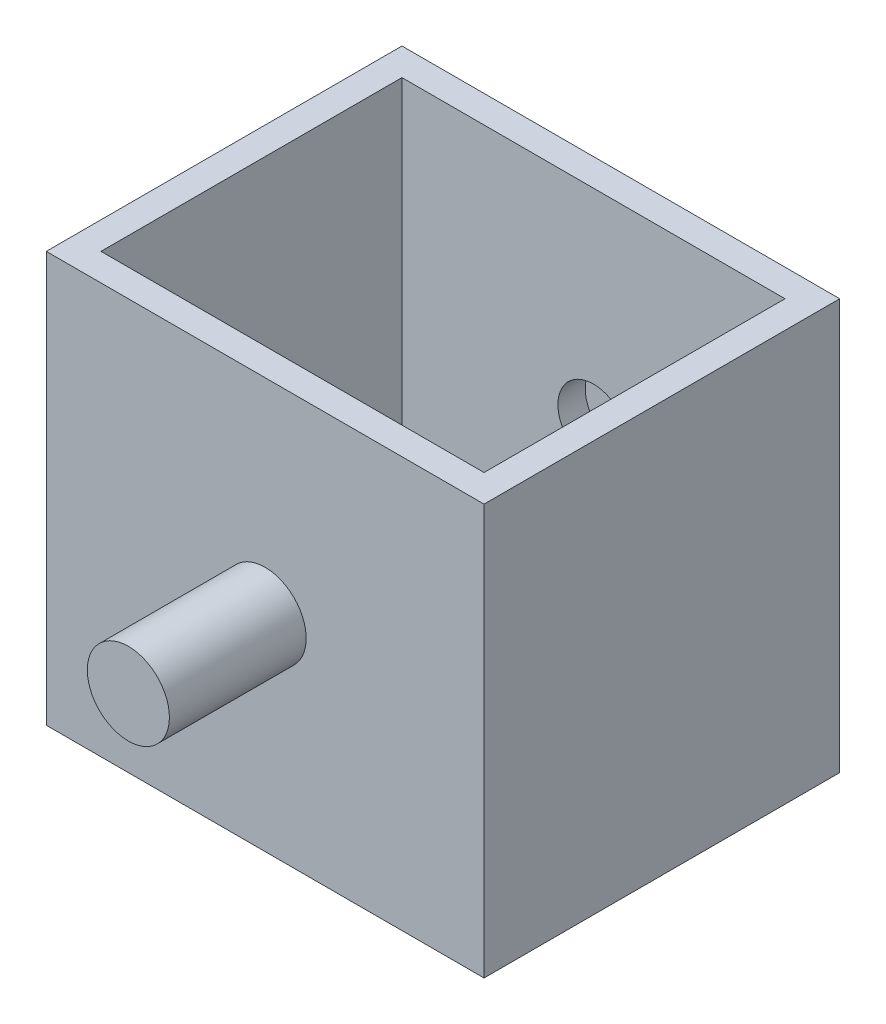
SolidWorks part; units mm, degrees
ref_plane "Front Plane" through (0, 0, 0) normal (0, 0, 1) x (1, 0, 0)
ref_plane "Top Plane" through (0, 0, 0) normal (0, 1, 0) x (1, 0, 0)
ref_plane "Right Plane" through (0, 0, 0) normal (1, 0, 0) x (0, 0, -1)
sketch "Sketch1" plane through (0, 0, 0) normal (0, 0, 1) x (1, 0, 0)
  line L1 (-20.32, -19.05) -> (20.32, -19.05)
  line L2 (-20.32, -19.05) -> (-20.32, 19.05)
  line L3 (-20.32, 19.05) -> (20.32, 19.05)
  line L4 (20.32, -19.05) -> (20.32, 19.05)
  line L5 (-20.32, -19.05) -> (20.32, 19.05) construction
  line L6 (-20.32, 19.05) -> (20.32, -19.05) construction
  point P0 (0, 0)
  dimension "D1" = 40.64
  dimension "D2" = 38.1
extrude "main body" add sketch "Sketch1" along normal blind 33.02
shell "hollow it" thickness 2.54 removed face at (0, 19.05, 16.51)
ref_point "cut point"
sketch "Sketch2" plane through (20.32, 0, 0) normal (1, 0, 0) x (0, 0, -1)
  circle A0 centre (-16.51, 0) radius 3.81
ref_point "bigger nibble point"
ref_point "bigger nibble here, too"
sketch "Sketch3" plane through (0, 0, 33.02) normal (0, 0, 1) x (1, 0, 0)
  circle A0 centre (0, 0) radius 3.81
  dimension "D1" = 7.62
extrude "nibble no 1" add sketch "Sketch3" along normal blind 12.7
sketch "Sketch4" plane through (0, 0, 0) normal (0, 0, -1) x (-1, 0, 0)
  circle A0 centre (0, 0) radius 3.81
  dimension "D1" = 7.62
extrude "nibble no 2" add sketch "Sketch4" along normal blind 12.7
ref_point "nibble center"
ref_plane "nibble flag plane" through (0, 0, 0) normal (0, -1, 0) x (-1, 0, 0)
sketch "Sketch5" plane through (0, 0, 0) normal (0, -1, 0) x (-1, 0, 0)
  line L1 (-0.8217, 4.4483) -> (0.4483, 4.4483)
  line L2 (-0.8217, 4.4483) -> (-0.8217, 8.2583)
  line L3 (-0.8217, 8.2583) -> (0.4483, 8.2583)
  line L4 (0.4483, 4.4483) -> (0.4483, 8.2583)
  line L5 (-0.8217, 4.4483) -> (0.4483, 8.2583) construction
  line L6 (-0.8217, 8.2583) -> (0.4483, 4.4483) construction
  point P0 (-0.1867, 6.3533)
  dimension "D1" = 1.27
  dimension "D2" = 3.81
extrude "flag" add sketch "Sketch5" along normal blind 25.4
sketch "Sketch6" plane through (0, 0, 2.54) normal (0, 0, 1) x (1, 0, 0)
  circle A0 centre (0, 0) radius 3.302
extrude "nibble holes" cut sketch "Sketch6" against normal blind 2.54 and the other way blind 30.48
